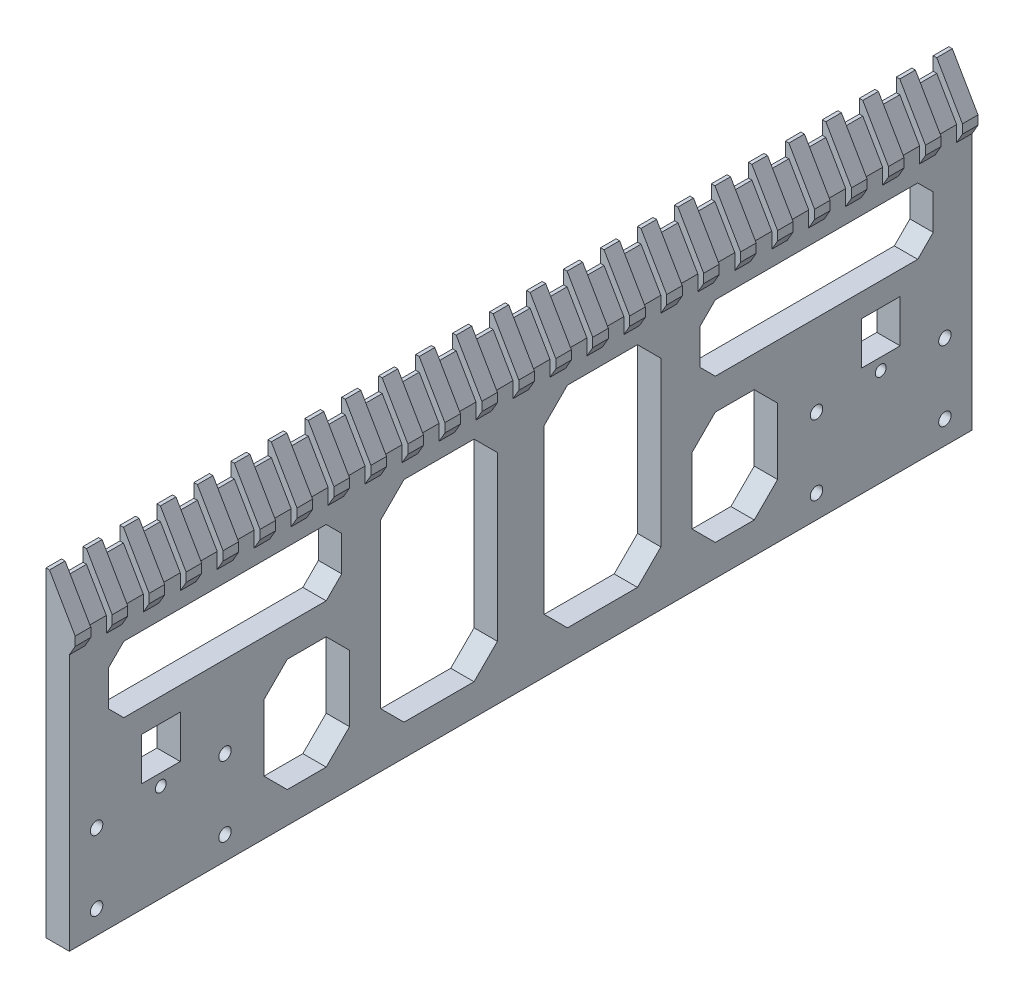
SolidWorks part; units mm, degrees
ref_plane "前视基准面" through (0, 0, 0) normal (0, 0, 1) x (1, 0, 0)
ref_plane "上视基准面" through (0, 0, 0) normal (0, 1, 0) x (1, 0, 0)
ref_plane "右视基准面" through (0, 0, 0) normal (1, 0, 0) x (0, 0, -1)
sketch "草图1" plane through (0, 0, 0) normal (1, 0, 0) x (0, 0, -1)
  line L0 (0, 0) -> (0, -70) construction
  line L1 (-116, 0) -> (116, 0)
  line L2 (-116, 0) -> (-116, -70)
  line L3 (-116, -70) -> (116, -70)
  line L4 (116, 0) -> (116, -70)
  dimension "D1" = 116
  dimension "D2" = 70
extrude "凸台-拉伸1" add sketch "草图1" along normal blind 6
sketch "草图3" plane through (6, 0, 0) normal (1, 0, 0) x (0, 0, -1)
  line L0 (0, 0) -> (0, -70) construction
  line L1 (-102, -8) -> (-50, -8)
  line L2 (-106, -12) -> (-106, -21)
  line L3 (-102, -25) -> (-50, -25)
  line L4 (-46, -12) -> (-46, -21)
  line L5 (116, 0) -> (-116, 0) construction
  line L6 (-116, -70) -> (116, -70) construction
  line L7 (-116, 0) -> (-116, -70) construction
  line L12 (-106, -12) -> (-102, -8)
  line L13 (-106, -21) -> (-102, -25)
  line L14 (-50, -25) -> (-46, -21)
  line L15 (-50, -8) -> (-46, -12)
  line L28 (-36, -14) -> (-30, -8)
  line L36 (-66, -56) -> (-60, -62)
  line L42 (-30, -8) -> (-12, -8)
  line L43 (-36, -14) -> (-36, -56)
  line L44 (-30, -62) -> (-12, -62)
  line L45 (-6, -14) -> (-6, -56)
  line L46 (-12, -8) -> (-6, -14)
  line L47 (-12, -62) -> (-6, -56)
  line L48 (-36, -56) -> (-30, -62)
  line L49 (-60, -33) -> (-50, -33)
  line L50 (-66, -39) -> (-66, -56)
  line L51 (-60, -62) -> (-50, -62)
  line L52 (-44, -39) -> (-44, -56)
  line L53 (-50, -62) -> (-44, -56)
  line L54 (-50, -33) -> (-44, -39)
  line L55 (-66, -39) -> (-60, -33)
  point P0 (-106, -8)
  point P1 (-46, -25)
  point P2 (-106, -25)
  point P3 (-46, -8)
  point P20 (-36, -8)
  point P21 (-6, -62)
  point P22 (-36, -62)
  point P23 (-6, -8)
  point P24 (-66, -33)
  point P33 (-44, -62)
  point P34 (-66, -62)
  point P35 (-44, -33)
  dimension "D1" = 10
  dimension "D2" = 8
  dimension "D3" = 17
  dimension "D4" = 60
  dimension "D5" = 8
  dimension "D6" = 8
  dimension "D7" = 54
  dimension "D12" = 80
  dimension "D13" = 6
  dimension "D14" = 30
  dimension "D15" = 10
  dimension "D16" = 8
  dimension "D21" = 8
  dimension "D22" = 29
  dimension "D23" = 22
extrude "切除-拉伸2" cut sketch "草图3" against normal through all
sketch "草图2" plane through (0, 0, 0) normal (1, 0, 0) x (0, 0, -1)
  line L0 (-92.5, -26.6289) -> (-92.5, -71.7155) construction
  line L1 (-109, -46) -> (-76, -46) construction
  line L2 (-109, -46) -> (-109, -64) construction
  line L3 (-109, -64) -> (-76, -64) construction
  line L4 (-76, -46) -> (-76, -64) construction
  line L5 (116, 0) -> (-116, 0) construction
  line L6 (0, 0) -> (0, -70) construction
  circle A0 centre (-109, -46) radius 1.55
  circle A1 centre (-76, -64) radius 1.55
  circle A2 centre (-76, -46) radius 1.55
  circle A3 centre (-109, -64) radius 1.55
  point P8 (-92.5, -46)
  dimension "D5" = 3.1
  dimension "D1" = 92.5
  dimension "D2" = 46
  dimension "D3" = 33
  dimension "D4" = 18
sketch "草图6" plane through (0, 0, 116) normal (0, 0, 1) x (1, 0, 0)
  line L0 (6, 0) -> (0, 0)
  line L1 (0, 0) -> (0, 8.8335)
  line L2 (0.9, 8.8335) -> (6, 0)
  line L3 (0, 8.8335) -> (0.9, 8.8335)
  line L4 (0, 8.8335) -> (0, 10.3923) construction
  line L5 (0, 10.3923) -> (0.9, 8.8335) construction
  dimension "D1" = 30
  dimension "D2" = 0.9
extrude "凸台-拉伸2" add sketch "草图6" against normal up to surface (232 mm away) up to face at (3, -35, -116)
ref_plane "基准面1" through (0, 0, 0) normal (0, 0, -1) x (-1, 0, 0)
sketch "草图8" plane through (0, 0, 116) normal (0, 0, 1) x (1, 0, 0)
  line L0 (0, 10.3923) -> (0, 12.3335)
  line L1 (0.9, 12.3335) -> (7.5, 0.9019)
  line L2 (7.5, 0.9019) -> (7.5, -1.4019)
  line L3 (7.5, -4) -> (6, -4) construction
  line L4 (6, 0) -> (6, -70) construction
  line L5 (6, -4) -> (6, 0)
  line L6 (6, 0) -> (0.9, 8.8335) construction
  line L7 (6, 0) -> (0.9, 8.8335)
  line L8 (0, 12.3335) -> (0.9, 12.3335)
  line L9 (0, 12.3335) -> (0, 13.8923) construction
  line L10 (0, 13.8923) -> (0.9, 12.3335) construction
  line L11 (0, 10.3923) -> (0, 8.8335)
  line L12 (0, 8.8335) -> (0.9, 8.8335)
  line L13 (0.9, 8.8335) -> (0, 10.3923) construction
  line L14 (6, -4) -> (7.5, -1.4019)
  line L15 (7.5, -1.4019) -> (7.5, -4) construction
  dimension "D1" = 3.5
  dimension "D2" = 1.5
  dimension "D3" = 4
  dimension "D4" = 0.9
  dimension "D5" = 30
extrude "凸台-拉伸3" add sketch "草图8" against normal blind 4
pattern_linear "阵列(线性)1" count 25 spacing 9.5 along (0, 0, -1) of "凸台-拉伸3"
hole_wizard "打孔尺寸(%根据)内六角圆柱头螺钉的类型1" positions "草图14" profile "草图15" counterbore size "M3" standard "GB" end condition through all
sketch "草图14" plane through (0, 0, 0) normal (-1, 0, 0) x (0, 0, 1)
  point P0 (76, -46)
  point P3 (109, -46)
  point P6 (109, -64)
  point P9 (76, -64)
sketch "草图15" plane through (0, -46, 76) normal (0, 1, 0) x (0, 0, 1)
  line L0 (0, 0) -> (0, 7.5)
  line L1 (0, 7.5) -> (1.6, 7.5)
  line L3 (1.6, 7.5) -> (1.6, 3.4)
  line L4 (1.6, 3.4) -> (3, 3.4)
  line L5 (3, 3.4) -> (3, 0)
  line L7 (3, 0) -> (0, 0)
  line L11 (0, -6.35) -> (0, 107.95) construction
  dimension "通孔孔直径" = 3.2
  dimension "通孔孔深度" = 7.5
  dimension "柱形沉头孔直径" = 6
  dimension "柱形沉头孔深度" = 3.4
sketch "草图16" plane through (0, 0, 0) normal (-1, 0, 0) x (0, 0, 1)
  line L0 (109, -46) -> (76, -46) construction
  line L2 (116, -70) -> (-116, -70) construction
  line L3 (92.5, -26.6289) -> (92.5, -71.7155) construction
  circle A0 centre (92.5, -45) radius 1.4
  dimension "D1" = 2.8
  dimension "D2" = 25
extrude "切除-拉伸3" cut sketch "草图16" against normal blind 10
mirror "镜向1" about plane through (0, 0, 0) normal (0, 0, -1) of "打孔尺寸(%根据)内六角圆柱头螺钉的类型1"
mirror "镜向2" about plane through (0, 0, 0) normal (0, 0, -1) of "切除-拉伸3", "切除-拉伸2"
sketch "草图17" plane through (0, 0, 0) normal (-1, 0, 0) x (0, 0, 1)
  line L1 (87.5, -31) -> (97.5, -31)
  line L2 (87.5, -31) -> (87.5, -42)
  line L3 (87.5, -42) -> (97.5, -42)
  line L4 (97.5, -31) -> (97.5, -42)
  line L6 (116, -70) -> (-116, -70) construction
  line L7 (0, -70) -> (0, -8.018) construction
  line L8 (-87.5, -31) -> (-97.5, -31)
  line L9 (-87.5, -31) -> (-87.5, -42)
  line L10 (-87.5, -42) -> (-97.5, -42)
  line L11 (-97.5, -31) -> (-97.5, -42)
  line L12 (92.5, -26.6289) -> (92.5, -71.7155) construction
  line L13 (92.5, -26.6289) -> (92.5, -71.7155) construction
  dimension "D1" = 10
  dimension "D2" = 11
  dimension "D4" = 28
extrude "切除-拉伸4" cut sketch "草图17" against normal through all
